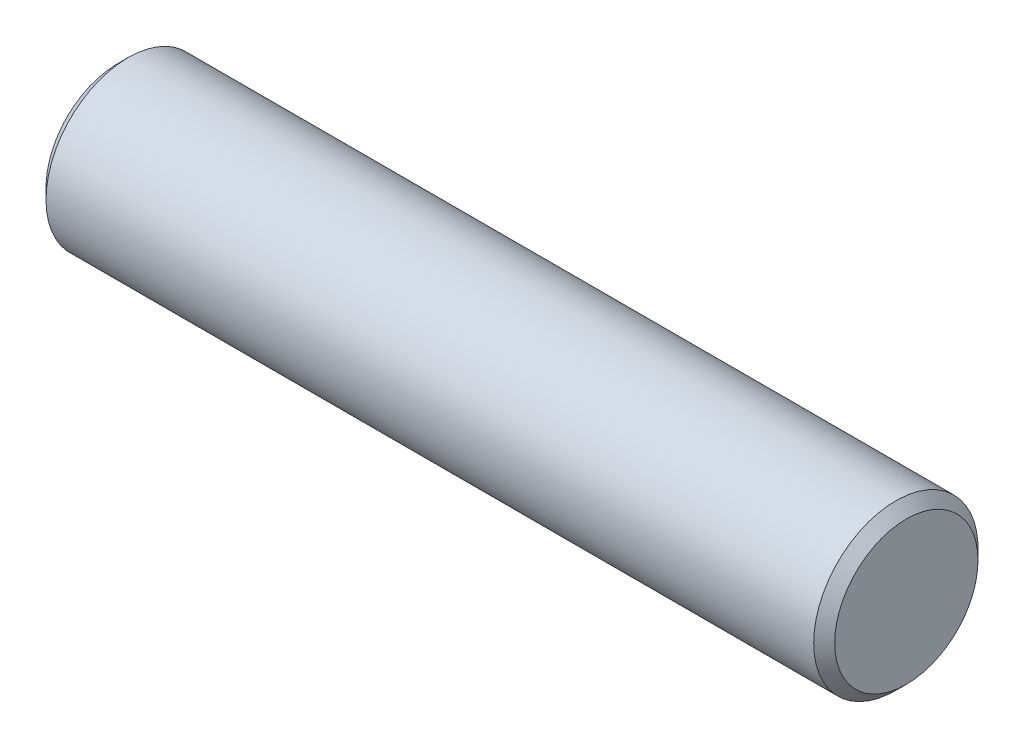
SolidWorks part; units mm, degrees
ref_plane "Front Plane" through (0, 0, 0) normal (0, 0, 1) x (1, 0, 0)
ref_plane "Top Plane" through (0, 0, 0) normal (0, 1, 0) x (1, 0, 0)
ref_plane "Right Plane" through (0, 0, 0) normal (1, 0, 0) x (0, 0, -1)
sketch "Sketch1" plane through (0, 0, 0) normal (1, 0, 0) x (0, 0, -1)
  circle A0 centre (0, 0) radius 3.9688
  dimension "D1" = 7.9375
extrude "Boss-Extrude1" add sketch "Sketch1" along normal mid plane 38.1
chamfer "Chamfer1" distance 0.508 angle 45 2 edges at (-19.05, 0, -3.9688) (19.05, 0, -3.9688)
